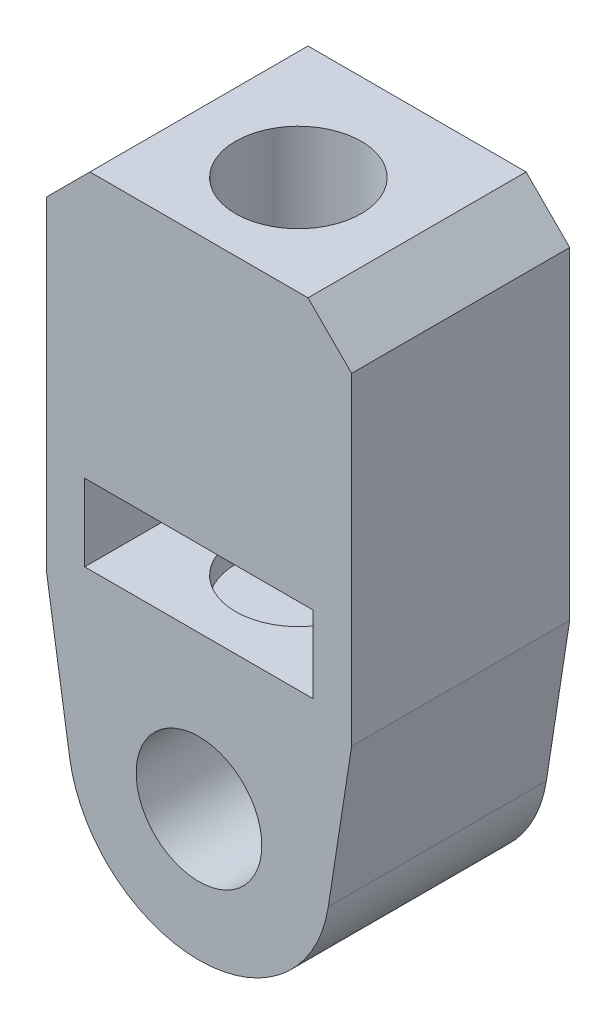
SolidWorks part; units mm, degrees
ref_plane "Front Plane" through (0, 0, 0) normal (0, 0, 1) x (1, 0, 0)
ref_plane "Top Plane" through (0, 0, 0) normal (0, 1, 0) x (1, 0, 0)
ref_plane "Right Plane" through (0, 0, 0) normal (1, 0, 0) x (0, 0, -1)
sketch "Sketch1" plane through (0, 0, 0) normal (0, 0, 1) x (1, 0, 0)
  line L0 (-5.5562, 4.7625) -> (-5.5562, 18.0975)
  line L1 (-5.5562, 18.0975) -> (5.5562, 18.0975)
  line L2 (5.5562, 18.0975) -> (5.5562, 4.7625)
  line L3 (-5.5562, 4.7625) -> (-4.7065, -0.7284)
  line L4 (4.7065, -0.7284) -> (5.5562, 4.7625)
  circle A1 centre (0, 0) radius 2.286
  arc A2 (-4.7065, -0.7284) -> (4.7065, -0.7284) centre (0, 0) ccw
  point P10 (0, 18.0975)
  dimension "D1" = 9.525
  dimension "D2" = 4.572
  dimension "D3" = 13.335
  dimension "D4" = 11.1125
  dimension "D5" = 4.7625
extrude "Boss-Extrude1" add sketch "Sketch1" along normal up to surface (7.9375 mm away)
sketch "Sketch2" plane through (0, 18.0975, 0) normal (0, 1, 0) x (1, 0, 0)
  circle A1 centre (0, -4.3187) radius 2.286
  circle A2 centre (0, -4.3187) radius 1.7525 construction
  dimension "D1" = 4.572
extrude "Cut-Extrude1" cut sketch "Sketch2" against normal offset from surface (13.335 mm away) 4.7625 up to plane "Top Plane"
sketch "Sketch3" plane through (0, 4.7625, 0) normal (0, 1, 0) x (1, 0, 0)
  line L11 (5.5562, -7.9375) -> (-5.5562, -7.9375) construction
  line L12 (-1.9064, -1.0167) -> (-4.1565, -4.9141)
  line L16 (4.1565, -4.9141) -> (1.9064, -1.0167)
  line L17 (1.9064, -1.0167) -> (-1.9064, -1.0167)
  line L18 (-4.1565, -4.9141) -> (-4.1565, -7.9375)
  line L19 (-4.1565, -7.9375) -> (4.1565, -7.9375)
  line L20 (4.1565, -7.9375) -> (4.1565, -4.9141)
  line L22 (-1.9064, -7.6207) -> (0, -7.6207) [skipped]
  line L23 (-3.8128, -4.3187) -> (-2.8596, -5.9697) [skipped]
  line L24 (2.1818, -7.1438) -> (2.8596, -5.9697) [skipped]
  circle A0 centre (0, -4.3187) radius 3.302 construction
  dimension "D1" = 6.604
extrude "Cut-Extrude2" cut sketch "Sketch3" along normal blind 2.794 from offset 0.7937
chamfer "Chamfer1" distance 1.5875 angle 45 2 edges at (5.5562, 18.0975, 3.9688) (-5.5562, 18.0975, 3.9688)
